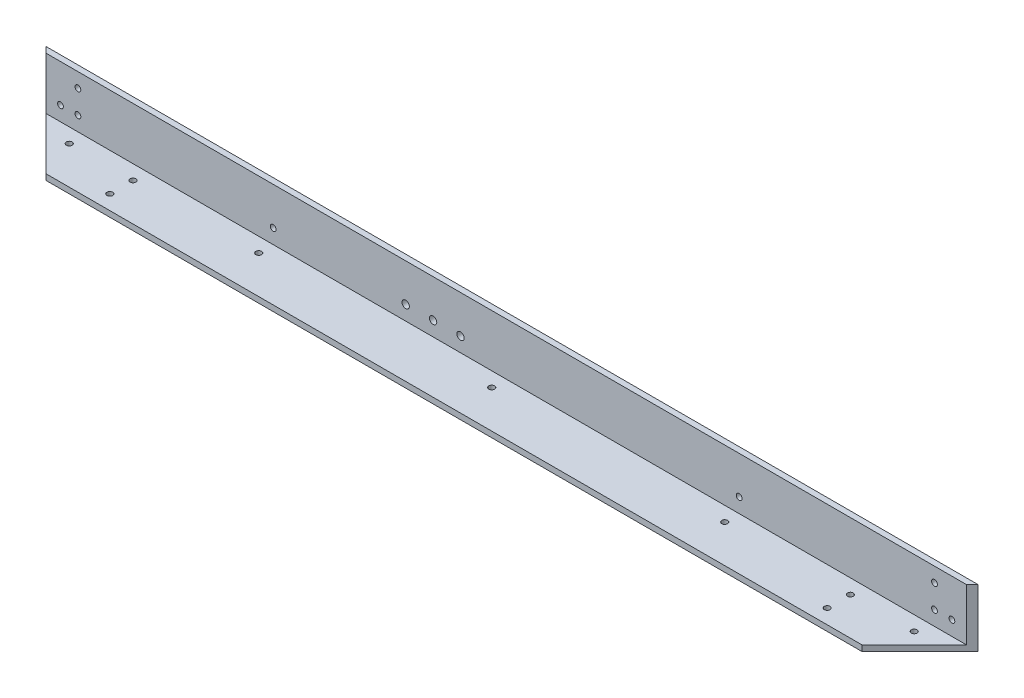
SolidWorks part; units mm, degrees
ref_plane "Front Plane" through (0, 0, 0) normal (0, 0, 1) x (1, 0, 0)
ref_plane "Top Plane" through (0, 0, 0) normal (0, 1, 0) x (1, 0, 0)
ref_plane "Right Plane" through (0, 0, 0) normal (1, 0, 0) x (0, 0, -1)
sketch "Sketch1" plane through (0, 0, 0) normal (1, 0, 0) x (0, 0, -1)
  line L0 (0, 0) -> (-31.75, 0)
  line L1 (-31.75, 0) -> (-31.75, 3.175)
  line L2 (-31.75, 3.175) -> (-3.175, 3.175)
  line L3 (-3.175, 3.175) -> (-3.175, 31.75)
  line L4 (-3.175, 31.75) -> (0, 31.75)
  line L5 (0, 31.75) -> (0, 0)
  dimension "LHeight" = 31.75
  dimension "LWidth" = 31.75
  dimension "LMaterialThickness" = 3.175
  dimension "D1" = 28.575
  dimension "D2" = 28.575
  dimension "D3" = 3.175
extrude "Boss-Extrude1" add sketch "Sketch1" along normal blind 510
chamfer "Chamfer6" distance 31.75 angle 45 1 edges at (510, 1.5875, 31.75)
chamfer "Chamfer7" distance 31.75 angle 45 1 edges at (0, 1.5875, 31.75)
sketch "TopHoles-Sketch3" plane through (0, 3.175, 0) normal (0, 1, 0) x (1, 0, 0)
  line L1 (478.25, -31.75) -> (31.75, -31.75) construction
  line L2 (510, 0) -> (0, 0) construction
  circle A5 centre (58.7375, -23.8125) radius 1.5875
  circle A6 centre (451.2625, -23.8125) radius 1.5875
  circle A9 centre (451.2625, -11.1125) radius 1.5875
  circle A10 centre (58.7375, -11.1125) radius 1.5875
  circle A11 centre (486.1875, -11.1125) radius 1.5875
  circle A12 centre (23.8125, -11.1125) radius 1.5875
  circle A13 centre (127.5, -11.1125) radius 1.5875
  circle A14 centre (255, -11.1125) radius 1.5875
  circle A15 centre (382.5, -11.1125) radius 1.5875
  dimension "D9" = 3.175
  dimension "D12" = 7.9375
  dimension "D2" = 11.1125
  dimension "D3" = 23.8125
  dimension "D6" = 23.8125
  dimension "D4" = 12.7
  dimension "D5" = 34.925
  dimension "D7" = 34.925
  dimension "D8" = 127.5
  dimension "D10" = 127.5
  dimension "D11" = 127.5
  dimension "D13" = 68.7625
extrude "TopHoles-Cut-Extrude2" cut sketch "TopHoles-Sketch3" against normal through all
sketch "BackHoles-Sketch4" plane through (0, 0, 3.175) normal (0, 0, 1) x (1, 0, 0)
  line L0 (0, 0) -> (0, 31.75) construction
  line L1 (510, 0) -> (510, 31.75) construction
  line L2 (478.25, 0) -> (31.75, 0) construction
  line L3 (510, 31.75) -> (0, 31.75) construction
  line L7 (510, 0) -> (0, 0) construction
  circle A3 centre (489.3625, 23.8125) radius 1.5875
  circle A4 centre (20.6375, 23.8125) radius 1.5875
  circle A6 centre (11.1125, 11.1125) radius 1.5875
  circle A7 centre (20.6375, 11.1125) radius 1.5875
  circle A8 centre (489.3625, 11.1125) radius 1.5875
  circle A9 centre (498.8875, 11.1125) radius 1.5875
  circle A10 centre (200, 11.1125) radius 2
  circle A11 centre (215, 11.1125) radius 2
  circle A12 centre (230, 11.1125) radius 2
  circle A13 centre (127.5, 11.1125) radius 1.5875
  circle A14 centre (382.5, 11.1125) radius 1.5875
  dimension "D11" = 4
  dimension "D2" = 3.175
  dimension "D7" = 11.1125
  dimension "D6" = 20.6375
  dimension "D5" = 20.6375
  dimension "D8" = 215
  dimension "D9" = 15
  dimension "D10" = 15
  dimension "D12" = 11.1125
  dimension "D13" = 127.5
  dimension "D14" = 127.5
  dimension "D4" = 7.9375
  dimension "D15" = 11.1125
  dimension "D3" = 11.1125
extrude "BackHoles-Cut-Extrude3" cut sketch "BackHoles-Sketch4" against normal through all
equation "\"TopRailWidth\"= 1.25in"
equation "\"TopRailHeight\"= 1.25in"
equation "\"RailThickness\"= .125in'Spec"
equation "\"SideRailHoleY1FromEdge\"= \"HoleOffsetFromEdge\""
equation "\"SideRailHoleX1FromSide\"= \"HoleOffsetFromSide\""
equation "\"VSWidth\"= 1.25in'Spec"
equation "\"HoleOffsetFromEdge\"= \"RailThickness\" * 2.5"
equation "\"HoleOffsetFromSide\"= \"RailThickness\" * 3.5"
equation "\"TopCBWidth\"= \"TopRailWidth\" - \"RailThickness\"'Equals 28.575"
equation "\"SideRailHoleX2FromSide\"= \"VSWidth\" - \"HoleOffsetFromEdge\" - \"RailThickness\"'Equals 20.6375"
equation "\"FasteningHoleDiameter\"= .125in"
equation "\"SideRailHoleY2FromSide\"= \"HoleOffsetFromSide\""
equation "\"LWidth@Sketch1\"=\"TopRailWidth\""
equation "\"LHeight@Sketch1\"=\"TopRailHeight\""
equation "\"LMaterialThickness@Sketch1\"=\"RailThickness\""
equation "\"D1@Boss-Extrude1\"= \"FrontBackRailLength\""
equation "\"FrontBackRailLength\"= 510mm"
equation "\"D7@BackHoles-Sketch4\"=\"SideRailHoleY2FromSide\""
equation "\"D1@Chamfer6\"=\"TopRailWidth\""
equation "\"D1@Chamfer7\"=\"TopRailWidth\""
equation "\"D6@TopHoles-Sketch3\"=\"TopHoleX1FromEdge\" + \"RailThickness\""
equation "\"D6@BackHoles-Sketch4\"=\"SideRailHoleX2FromSide\""
equation "\"D5@BackHoles-Sketch4\"=\"SideRailHoleX2FromSide\""
equation "\"D8@BackHoles-Sketch4\"=\"FrontBackRailLength\"/2 - 40mm"
equation "\"TopHoleX1FromEdge\"= \"TopCBWidth\" - \"HoleOffsetFromEdge\"'Equals 20.6375"
equation "\"TopHoleX2FromX1\"= \"TopCBLength\" - \"TopHoleX1FromEdge\" - \"HoleOffsetFromEdge\"'Equals 34.925"
equation "\"TopHoleY1FromSide\"= \"HoleOffsetFromSide\""
equation "\"TopHoleY2FromY1\"= \"TopCBWidth\" - \"TopHoleY1FromEdge\" - \"HoleOffsetFromEdge\"'Equals 12.7"
equation "\"D2@TopHoles-Sketch3\"=\"TopHoleY1FromSide\""
equation "\"D4@TopHoles-Sketch3\"=\"TopHoleY2FromY1\""
equation "\"D5@TopHoles-Sketch3\"=\"TopHoleX2FromX1\""
equation "\"D7@TopHoles-Sketch3\"=\"TopHoleX2FromX1\""
equation "\"TopCBLength\"= \"TopRailWidth\" * 2'Equals 63.5"
equation "\"TopHoleY1FromEdge\"= \"HoleOffsetFromEdge\""
equation "\"D3@TopHoles-Sketch3\"=\"TopHoleX1FromEdge\" + \"RailThickness\""
equation "\"FrontOrBackEnclosureOffsets\"= \"FrontBackRailLength\" / 4"
equation "\"D8@TopHoles-Sketch3\"=\"FrontOrBackEnclosureOffsets\""
equation "\"D11@TopHoles-Sketch3\"=\"FrontOrBackEnclosureOffsets\""
equation "\"D10@TopHoles-Sketch3\"=\"FrontOrBackEnclosureOffsets\""
equation "\"D13@BackHoles-Sketch4\"=\"FrontOrBackEnclosureOffsets\""
equation "\"D14@BackHoles-Sketch4\"=\"FrontOrBackEnclosureOffsets\""
equation "\"D2@BackHoles-Sketch4\"=\"FasteningHoleDiameter\""
equation "\"D4@BackHoles-Sketch4\"=\"SideRailHoleY1FromEdge\""
equation "\"D15@BackHoles-Sketch4\"=\"SideRailHoleX1FromSide\""
equation "\"D3@BackHoles-Sketch4\"=\"SideRailHoleX1FromSide\""
